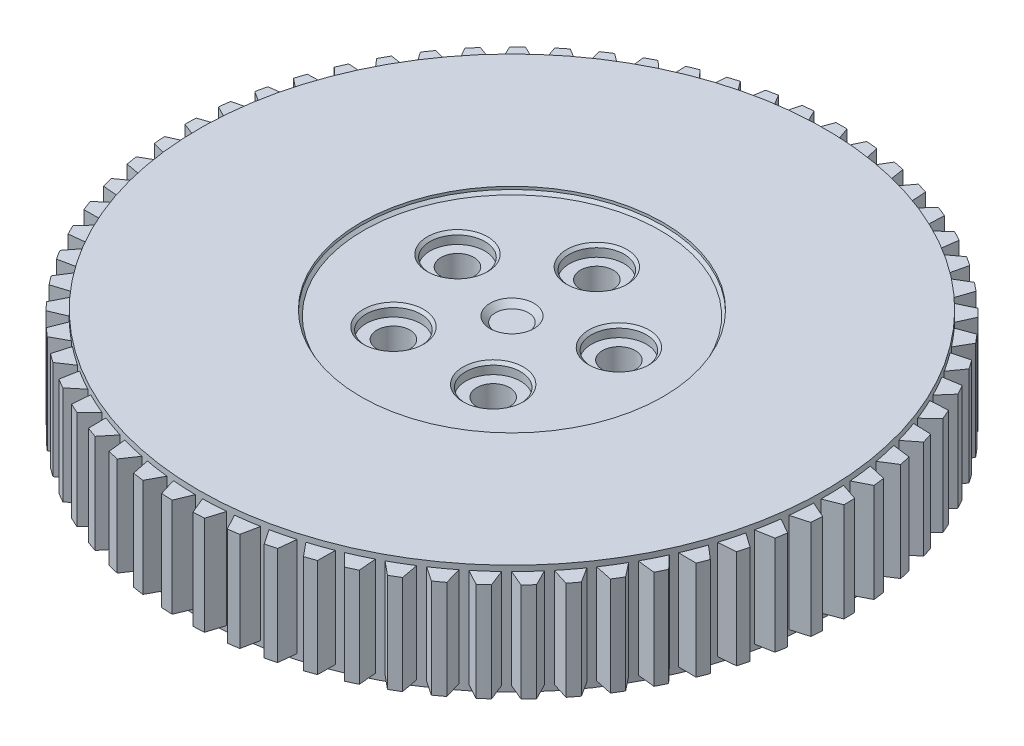
SolidWorks part; units mm, degrees
ref_plane "Front Plane" through (0, 0, 0) normal (0, 0, 1) x (1, 0, 0)
ref_plane "Top Plane" through (0, 0, 0) normal (0, 1, 0) x (1, 0, 0)
ref_plane "Right Plane" through (0, 0, 0) normal (1, 0, 0) x (0, 0, -1)
sketch "Sketch1" plane through (0, 0, 0) normal (0, 1, 0) x (1, 0, 0)
  circle A0 centre (0, 0) radius 114
  dimension "D1" = 228
extrude "Boss-Extrude1" add sketch "Sketch1" along normal blind 40
sketch "Sketch2" plane through (0, 40, 0) normal (0, 1, 0) x (1, 0, 0)
  line L1 (0, 30.9017) -> (-29.3893, 9.5492)
  line L2 (-29.3893, 9.5492) -> (-18.1636, -25)
  line L3 (-18.1636, -25) -> (18.1636, -25)
  line L4 (18.1636, -25) -> (29.3893, 9.5492)
  line L5 (29.3893, 9.5492) -> (0, 30.9017)
  circle A0 centre (0, 0) radius 25 construction
  circle A1 centre (0, 30.9017) radius 6
  circle A2 centre (-29.3893, 9.5492) radius 6
  circle A3 centre (-18.1636, -25) radius 6
  circle A4 centre (18.1636, -25) radius 6
  circle A5 centre (29.3893, 9.5492) radius 6
  dimension "D1" = 12
  dimension "D2" = 12
  dimension "D3" = 12
  dimension "D4" = 12
  dimension "D5" = 12
extrude "Cut-Extrude1" cut sketch "Sketch2" against normal blind 40 contours L1 A2 L2 | L2 A2 L1 | L1 A1 L5 | L5 A1 L1 | L5 A5 L4 | L4 A5 L5 | L3 A4 L4 | L4 A4 L3 | L2 A3 L3 | L3 A3 L2 region at (0, 40, -27.4681) region at (0, 40, -32.3732) region at (-26.1237, 40, -8.4881) region at (-30.7888, 40, -10.0039) region at (30.7888, 40, -10.0039) region at (26.1237, 40, -8.4881) region at (-16.1454, 40, 22.2222) region at (-19.0285, 40, 26.1905) region at (19.0285, 40, 26.1905) region at (16.1454, 40, 22.2222)
sketch "Sketch3" plane through (0, 0, 0) normal (0, -1, 0) x (1, 0, 0)
  circle A0 centre (0, 0) radius 45
  dimension "D1" = 90
extrude "Cut-Extrude2" cut sketch "Sketch3" against normal blind 15
sketch "Sketch4" plane through (0, 40, 0) normal (0, 1, 0) x (1, 0, 0)
  circle A5 centre (0, 30.9017) radius 10
  circle A6 centre (0, 30.9017) radius 10
  circle A8 centre (-29.3893, 9.5492) radius 10
  circle A9 centre (-29.3893, 9.5492) radius 10
  circle A11 centre (-18.1636, -25) radius 10
  circle A12 centre (-18.1636, -25) radius 10
  circle A14 centre (18.1636, -25) radius 10
  circle A15 centre (18.1636, -25) radius 10
  circle A17 centre (29.3893, 9.5492) radius 10
  circle A18 centre (29.3893, 9.5492) radius 10
  dimension "D1" = 4
  dimension "D2" = 4
  dimension "D3" = 4
  dimension "D4" = 4
  dimension "D5" = 4
extrude "Cut-Extrude3" cut sketch "Sketch4" against normal blind 6
chamfer "Chamfer1" distance 3 angle 45 5 edges at (-18.1636, 40, 35) (18.1636, 40, 35) (29.3893, 40, 0.4508) (-29.3893, 40, 0.4508) (0, 40, -20.9017)
sketch "Sketch5" plane through (0, 40, 0) normal (0, 1, 0) x (1, 0, 0)
  circle A0 centre (0, 0) radius 6
  dimension "D1" = 12
extrude "Cut-Extrude4" cut sketch "Sketch5" against normal blind 4
chamfer "Chamfer2" distance 4 angle 45 1 edges at (0, 40, 6)
sketch "Sketch8" plane through (0, 40, 0) normal (0, 1, 0) x (1, 0, 0)
  line L0 (0, 112) -> (0, 120)
  line L1 (-2, 120) -> (2, 120)
  line L2 (-2, 120) -> (-4.9516, 111.8905)
  line L3 (2, 120) -> (4.9516, 111.8905)
  line L4 (-4.9516, 111.8905) -> (4.9516, 111.8905)
  line L5 (5.8705, 111.846) -> (15.7275, 110.8902)
  line L6 (13.5723, 119.2468) -> (15.7275, 110.8902)
  line L7 (9.591, 119.6328) -> (13.5723, 119.2468)
  line L8 (9.591, 119.6328) -> (5.8705, 111.846)
  line L9 (16.6378, 110.7573) -> (26.3565, 108.8546)
  line L10 (25.0179, 117.3802) -> (26.3565, 108.8546)
  line L11 (21.0925, 118.1487) -> (25.0179, 117.3802)
  line L12 (21.0925, 118.1487) -> (16.6378, 110.7573)
  line L13 (27.2497, 108.6345) -> (36.7395, 105.8027)
  line L14 (36.23, 114.4176) -> (36.7395, 105.8027)
  line L15 (32.397, 115.5614) -> (36.23, 114.4176)
  line L16 (32.397, 115.5614) -> (27.2497, 108.6345)
  line L17 (37.6073, 105.4974) -> (46.7794, 101.7629)
  line L18 (47.1037, 110.3868) -> (46.7794, 101.7629)
  line L19 (43.399, 111.8951) -> (47.1037, 110.3868)
  line L20 (43.399, 111.8951) -> (37.6073, 105.4974)
  line L21 (47.6137, 101.3752) -> (56.3825, 96.773)
  line L22 (57.5377, 105.3253) -> (56.3825, 96.773)
  line L23 (53.9959, 107.1842) -> (57.5377, 105.3253)
  line L24 (53.9959, 107.1842) -> (47.6137, 101.3752)
  line L25 (57.1755, 96.3066) -> (65.4593, 90.8795)
  line L26 (67.4344, 99.2804) -> (65.4593, 90.8795)
  line L27 (64.0886, 101.4724) -> (67.4344, 99.2804)
  line L28 (64.0886, 101.4724) -> (57.1755, 96.3066)
  line L29 (66.2035, 90.3388) -> (73.9248, 84.1375)
  line L30 (76.7016, 92.3086) -> (73.9248, 84.1375)
  line L31 (73.5829, 94.8133) -> (76.7016, 92.3086)
  line L32 (73.5829, 94.8133) -> (66.2035, 90.3388)
  line L33 (74.6134, 83.5275) -> (81.7002, 76.61)
  line L34 (85.2526, 84.4749) -> (81.7002, 76.61)
  line L35 (82.3902, 87.2689) -> (85.2526, 84.4749)
  line L36 (82.3902, 87.2689) -> (74.6134, 83.5275)
  line L37 (82.3266, 75.9363) -> (88.7127, 68.3671)
  line L38 (93.0076, 75.8524) -> (88.7127, 68.3671)
  line L39 (90.4282, 78.9097) -> (93.0076, 75.8524)
  line L40 (90.4282, 78.9097) -> (82.3266, 75.9363)
  line L41 (89.2712, 67.6361) -> (94.8969, 59.4859)
  line L42 (99.8942, 66.5218) -> (94.8969, 59.4859)
  line L43 (97.6219, 69.8137) -> (99.8942, 66.5218)
  line L44 (97.6219, 69.8137) -> (89.2712, 67.6361)
  line L45 (95.3823, 58.7045) -> (100.1951, 50.0494)
  line L46 (105.8481, 56.5701) -> (100.1951, 50.0494)
  line L47 (103.9042, 60.0659) -> (105.8481, 56.5701)
  line L48 (103.9042, 60.0659) -> (95.3823, 58.7045)
  line L49 (100.6028, 49.2247) -> (104.5578, 40.1455)
  line L50 (110.8138, 46.0902) -> (104.5578, 40.1455)
  line L51 (109.2163, 49.7573) -> (110.8138, 46.0902)
  line L52 (109.2163, 49.7573) -> (100.6028, 49.2247)
  line L53 (104.884, 39.2853) -> (107.9443, 29.8668)
  line L54 (114.7448, 35.1799) -> (107.9443, 29.8668)
  line L55 (113.5087, 38.9842) -> (114.7448, 35.1799)
  line L56 (113.5087, 38.9842) -> (104.884, 39.2853)
  line L57 (108.186, 28.9792) -> (110.323, 19.3092)
  line L58 (117.6045, 23.9412) -> (110.323, 19.3092)
  line L59 (116.7414, 27.847) -> (117.6045, 23.9412)
  line L60 (116.7414, 27.847) -> (108.186, 28.9792)
  line L61 (110.4778, 18.4024) -> (111.6715, 8.5714)
  line L62 (119.3661, 12.479) -> (111.6715, 8.5714)
  line L63 (118.884, 16.4498) -> (119.3661, 12.479)
  line L64 (118.884, 16.4498) -> (110.4778, 18.4024)
  line L65 (111.7382, 7.6539) -> (111.9775, -2.2465)
  line L66 (120.0133, 0.9002) -> (111.9775, -2.2465)
  line L67 (119.9166, 4.8991) -> (120.0133, 0.9002)
  line L68 (119.9166, 4.8991) -> (111.7382, 7.6539)
  line L69 (111.9552, -3.1662) -> (111.2379, -13.0434)
  line L70 (119.5399, -10.6869) -> (111.2379, -13.0434)
  line L71 (119.8296, -6.6974) -> (119.5399, -10.6869)
  line L72 (119.8296, -6.6974) -> (111.9552, -3.1662)
  line L73 (111.127, -13.9566) -> (109.4597, -23.7185)
  line L74 (117.9504, -22.1743) -> (109.4597, -23.7185)
  line L75 (118.6238, -18.2314) -> (117.9504, -22.1743)
  line L76 (118.6238, -18.2314) -> (111.127, -13.9566)
  line L77 (109.2612, -24.6168) -> (106.6596, -34.1722)
  line L78 (115.2597, -33.4546) -> (106.6596, -34.1722)
  line L79 (116.3105, -29.5951) -> (115.2597, -33.4546)
  line L80 (116.3105, -29.5951) -> (109.2612, -24.6168)
  line L81 (106.3753, -35.0471) -> (102.8636, -44.3068)
  line L82 (111.4927, -44.4226) -> (102.8636, -44.3068)
  line L83 (112.9112, -40.6826) -> (111.4927, -44.4226)
  line L84 (112.9112, -40.6826) -> (106.3753, -35.0471)
  line L85 (102.4962, -45.1502) -> (98.1071, -54.0277)
  line L86 (106.6848, -54.9758) -> (98.1071, -54.0277)
  line L87 (108.4576, -51.3901) -> (106.6848, -54.9758)
  line L88 (108.4576, -51.3901) -> (102.4962, -45.1502)
  line L89 (97.6601, -54.8317) -> (92.4347, -63.2442)
  line L90 (100.8809, -65.0158) -> (92.4347, -63.2442)
  line L91 (102.9914, -61.6179) -> (100.8809, -65.0158)
  line L92 (102.9914, -61.6179) -> (97.6601, -54.8317)
  line L93 (91.9121, -64.0013) -> (85.8992, -71.8702)
  line L94 (94.135, -74.4487) -> (85.8992, -71.8702)
  line L95 (96.5636, -71.2703) -> (94.135, -74.4487)
  line L96 (96.5636, -71.2703) -> (91.9121, -64.0013)
  line L97 (85.306, -72.5733) -> (78.5618, -79.8251)
  line L98 (86.5102, -83.1864) -> (78.5618, -79.8251)
  line L99 (89.2343, -80.2574) -> (86.5102, -83.1864)
  line L100 (89.2343, -80.2574) -> (85.306, -72.5733)
  line L101 (77.9035, -80.4677) -> (70.4908, -87.0348)
  line L102 (78.0777, -91.1475) -> (70.4908, -87.0348)
  line L103 (81.0717, -88.495) -> (78.0777, -91.1475)
  line L104 (81.0717, -88.495) -> (77.9035, -80.4677)
  line L105 (69.7735, -87.6108) -> (61.7616, -93.4318)
  line L106 (68.9162, -98.2576) -> (61.7616, -93.4318)
  line L107 (72.1523, -95.9065) -> (68.9162, -98.2576)
  line L108 (72.1523, -95.9065) -> (69.7735, -87.6108)
  line L109 (60.9921, -93.9359) -> (52.4558, -98.9565)
  line L110 (59.1112, -104.4503) -> (52.4558, -98.9565)
  line L111 (62.5591, -102.4224) -> (59.1112, -104.4503)
  line L112 (62.5591, -102.4224) -> (60.9921, -93.9359)
  line L113 (51.6413, -99.384) -> (42.6603, -103.5572)
  line L114 (48.7544, -109.6677) -> (42.6603, -103.5572)
  line L115 (52.3819, -107.9821) -> (48.7544, -109.6677)
  line L116 (52.3819, -107.9821) -> (51.6413, -99.384)
  line L117 (41.8083, -103.9041) -> (32.4664, -107.1911)
  line L118 (37.9423, -113.8612) -> (32.4664, -107.1911)
  line L119 (41.7156, -112.5336) -> (37.9423, -113.8612)
  line L120 (41.7156, -112.5336) -> (41.8083, -103.9041)
  line L121 (31.5849, -107.4542) -> (21.9694, -109.8242)
  line L122 (26.776, -116.9916) -> (21.9694, -109.8242)
  line L123 (30.6598, -116.0344) -> (26.776, -116.9916)
  line L124 (30.6598, -116.0344) -> (31.5849, -107.4542)
  line L125 (21.0666, -110.0009) -> (11.2673, -111.4318)
  line L126 (15.3597, -119.0297) -> (11.2673, -111.4318)
  line L127 (19.3177, -118.4518) -> (15.3597, -119.0297)
  line L128 (19.3177, -118.4518) -> (21.0666, -110.0009)
  line L129 (10.3516, -111.5206) -> (0.46, -111.9991)
  line L130 (3.7999, -119.9565) -> (0.46, -111.9991)
  line L131 (7.7953, -119.7632) -> (3.7999, -119.9565)
  line L132 (7.7953, -119.7632) -> (10.3516, -111.5206)
  line L133 (-0.46, -111.9991) -> (-10.3516, -111.5206)
  line L134 (-7.7953, -119.7632) -> (-10.3516, -111.5206)
  line L135 (-3.7999, -119.9565) -> (-7.7953, -119.7632)
  line L136 (-3.7999, -119.9565) -> (-0.46, -111.9991)
  line L137 (-11.2673, -111.4318) -> (-21.0666, -110.0009)
  line L138 (-19.3177, -118.4518) -> (-21.0666, -110.0009)
  line L139 (-15.3597, -119.0297) -> (-19.3177, -118.4518)
  line L140 (-15.3597, -119.0297) -> (-11.2673, -111.4318)
  line L141 (-21.9694, -109.8242) -> (-31.5849, -107.4542)
  line L142 (-30.6598, -116.0344) -> (-31.5849, -107.4542)
  line L143 (-26.776, -116.9916) -> (-30.6598, -116.0344)
  line L144 (-26.776, -116.9916) -> (-21.9694, -109.8242)
  line L145 (-32.4664, -107.1911) -> (-41.8083, -103.9041)
  line L146 (-41.7156, -112.5336) -> (-41.8083, -103.9041)
  line L147 (-37.9423, -113.8612) -> (-41.7156, -112.5336)
  line L148 (-37.9423, -113.8612) -> (-32.4664, -107.1911)
  line L149 (-42.6603, -103.5572) -> (-51.6413, -99.384)
  line L150 (-52.3819, -107.9821) -> (-51.6413, -99.384)
  line L151 (-48.7544, -109.6677) -> (-52.3819, -107.9821)
  line L152 (-48.7544, -109.6677) -> (-42.6603, -103.5572)
  line L153 (-52.4558, -98.9565) -> (-60.9921, -93.9359)
  line L154 (-62.5591, -102.4224) -> (-60.9921, -93.9359)
  line L155 (-59.1112, -104.4503) -> (-62.5591, -102.4224)
  line L156 (-59.1112, -104.4503) -> (-52.4558, -98.9565)
  line L157 (-61.7616, -93.4318) -> (-69.7735, -87.6108)
  line L158 (-72.1523, -95.9065) -> (-69.7735, -87.6108)
  line L159 (-68.9162, -98.2576) -> (-72.1523, -95.9065)
  line L160 (-68.9162, -98.2576) -> (-61.7616, -93.4318)
  line L161 (-70.4908, -87.0348) -> (-77.9035, -80.4677)
  line L162 (-81.0717, -88.495) -> (-77.9035, -80.4677)
  line L163 (-78.0777, -91.1475) -> (-81.0717, -88.495)
  line L164 (-78.0777, -91.1475) -> (-70.4908, -87.0348)
  line L165 (-78.5618, -79.8251) -> (-85.306, -72.5733)
  line L166 (-89.2343, -80.2574) -> (-85.306, -72.5733)
  line L167 (-86.5102, -83.1864) -> (-89.2343, -80.2574)
  line L168 (-86.5102, -83.1864) -> (-78.5618, -79.8251)
  line L169 (-85.8992, -71.8702) -> (-91.9121, -64.0013)
  line L170 (-96.5636, -71.2703) -> (-91.9121, -64.0013)
  line L171 (-94.135, -74.4487) -> (-96.5636, -71.2703)
  line L172 (-94.135, -74.4487) -> (-85.8992, -71.8702)
  line L173 (-92.4347, -63.2442) -> (-97.6601, -54.8317)
  line L174 (-102.9914, -61.6179) -> (-97.6601, -54.8317)
  line L175 (-100.8809, -65.0158) -> (-102.9914, -61.6179)
  line L176 (-100.8809, -65.0158) -> (-92.4347, -63.2442)
  line L177 (-98.1071, -54.0277) -> (-102.4962, -45.1502)
  line L178 (-108.4576, -51.3901) -> (-102.4962, -45.1502)
  line L179 (-106.6848, -54.9758) -> (-108.4576, -51.3901)
  line L180 (-106.6848, -54.9758) -> (-98.1071, -54.0277)
  line L181 (-102.8636, -44.3068) -> (-106.3753, -35.0471)
  line L182 (-112.9112, -40.6826) -> (-106.3753, -35.0471)
  line L183 (-111.4927, -44.4226) -> (-112.9112, -40.6826)
  line L184 (-111.4927, -44.4226) -> (-102.8636, -44.3068)
  line L185 (-106.6596, -34.1722) -> (-109.2612, -24.6168)
  line L186 (-116.3105, -29.5951) -> (-109.2612, -24.6168)
  line L187 (-115.2597, -33.4546) -> (-116.3105, -29.5951)
  line L188 (-115.2597, -33.4546) -> (-106.6596, -34.1722)
  line L189 (-109.4597, -23.7185) -> (-111.127, -13.9566)
  line L190 (-118.6238, -18.2314) -> (-111.127, -13.9566)
  line L191 (-117.9504, -22.1743) -> (-118.6238, -18.2314)
  line L192 (-117.9504, -22.1743) -> (-109.4597, -23.7185)
  line L193 (-111.2379, -13.0434) -> (-111.9552, -3.1662)
  line L194 (-119.8296, -6.6974) -> (-111.9552, -3.1662)
  line L195 (-119.5399, -10.6869) -> (-119.8296, -6.6974)
  line L196 (-119.5399, -10.6869) -> (-111.2379, -13.0434)
  line L197 (-111.9775, -2.2465) -> (-111.7382, 7.6539)
  line L198 (-119.9166, 4.8991) -> (-111.7382, 7.6539)
  line L199 (-120.0133, 0.9002) -> (-119.9166, 4.8991)
  line L200 (-120.0133, 0.9002) -> (-111.9775, -2.2465)
  line L201 (-111.6715, 8.5714) -> (-110.4778, 18.4024)
  line L202 (-118.884, 16.4498) -> (-110.4778, 18.4024)
  line L203 (-119.3661, 12.479) -> (-118.884, 16.4498)
  line L204 (-119.3661, 12.479) -> (-111.6715, 8.5714)
  line L205 (-110.323, 19.3092) -> (-108.186, 28.9792)
  line L206 (-116.7414, 27.847) -> (-108.186, 28.9792)
  line L207 (-117.6045, 23.9412) -> (-116.7414, 27.847)
  line L208 (-117.6045, 23.9412) -> (-110.323, 19.3092)
  line L209 (-107.9443, 29.8668) -> (-104.884, 39.2853)
  line L210 (-113.5087, 38.9842) -> (-104.884, 39.2853)
  line L211 (-114.7448, 35.1799) -> (-113.5087, 38.9842)
  line L212 (-114.7448, 35.1799) -> (-107.9443, 29.8668)
  line L213 (-104.5578, 40.1455) -> (-100.6028, 49.2247)
  line L214 (-109.2163, 49.7573) -> (-100.6028, 49.2247)
  line L215 (-110.8138, 46.0902) -> (-109.2163, 49.7573)
  line L216 (-110.8138, 46.0902) -> (-104.5578, 40.1455)
  line L217 (-100.1951, 50.0494) -> (-95.3823, 58.7045)
  line L218 (-103.9042, 60.0659) -> (-95.3823, 58.7045)
  line L219 (-105.8481, 56.5701) -> (-103.9042, 60.0659)
  line L220 (-105.8481, 56.5701) -> (-100.1951, 50.0494)
  line L221 (-94.8969, 59.4859) -> (-89.2712, 67.6361)
  line L222 (-97.6219, 69.8137) -> (-89.2712, 67.6361)
  line L223 (-99.8942, 66.5218) -> (-97.6219, 69.8137)
  line L224 (-99.8942, 66.5218) -> (-94.8969, 59.4859)
  line L225 (-88.7127, 68.3671) -> (-82.3266, 75.9363)
  line L226 (-90.4282, 78.9097) -> (-82.3266, 75.9363)
  line L227 (-93.0076, 75.8524) -> (-90.4282, 78.9097)
  line L228 (-93.0076, 75.8524) -> (-88.7127, 68.3671)
  line L229 (-81.7002, 76.61) -> (-74.6134, 83.5275)
  line L230 (-82.3902, 87.2689) -> (-74.6134, 83.5275)
  line L231 (-85.2526, 84.4749) -> (-82.3902, 87.2689)
  line L232 (-85.2526, 84.4749) -> (-81.7002, 76.61)
  line L233 (-73.9248, 84.1375) -> (-66.2035, 90.3388)
  line L234 (-73.5829, 94.8133) -> (-66.2035, 90.3388)
  line L235 (-76.7016, 92.3086) -> (-73.5829, 94.8133)
  line L236 (-76.7016, 92.3086) -> (-73.9248, 84.1375)
  line L237 (-65.4593, 90.8795) -> (-57.1755, 96.3066)
  line L238 (-64.0886, 101.4724) -> (-57.1755, 96.3066)
  line L239 (-67.4344, 99.2804) -> (-64.0886, 101.4724)
  line L240 (-67.4344, 99.2804) -> (-65.4593, 90.8795)
  line L241 (-56.3825, 96.773) -> (-47.6137, 101.3752)
  line L242 (-53.9959, 107.1842) -> (-47.6137, 101.3752)
  line L243 (-57.5377, 105.3253) -> (-53.9959, 107.1842)
  line L244 (-57.5377, 105.3253) -> (-56.3825, 96.773)
  line L245 (-46.7794, 101.7629) -> (-37.6073, 105.4974)
  line L246 (-43.399, 111.8951) -> (-37.6073, 105.4974)
  line L247 (-47.1037, 110.3868) -> (-43.399, 111.8951)
  line L248 (-47.1037, 110.3868) -> (-46.7794, 101.7629)
  line L249 (-36.7395, 105.8027) -> (-27.2497, 108.6345)
  line L250 (-32.397, 115.5614) -> (-27.2497, 108.6345)
  line L251 (-36.23, 114.4176) -> (-32.397, 115.5614)
  line L252 (-36.23, 114.4176) -> (-36.7395, 105.8027)
  line L253 (-26.3565, 108.8546) -> (-16.6378, 110.7573)
  line L254 (-21.0925, 118.1487) -> (-16.6378, 110.7573)
  line L255 (-25.0179, 117.3802) -> (-21.0925, 118.1487)
  line L256 (-25.0179, 117.3802) -> (-26.3565, 108.8546)
  line L257 (-15.7275, 110.8902) -> (-5.8705, 111.846)
  line L258 (-9.591, 119.6328) -> (-5.8705, 111.846)
  line L259 (-13.5723, 119.2468) -> (-9.591, 119.6328)
  line L260 (-13.5723, 119.2468) -> (-15.7275, 110.8902)
  circle A0 centre (0, 0) radius 112
  circle A1 centre (0, 0) radius 120
  point P9 (0, 120)
  point P270 (0, 0)
  circle M12 centre (0, 0) radius 114
  dimension "D1" = 240
  dimension "D2" = 224
  dimension "D3" = 4
  dimension "D4" = 110
  dimension "D5" = 110
  dimension "D6" = 65
extrude "Boss-Extrude2" add sketch "Sketch8" against normal blind 38 contours L238 A1 L240 M12 | L242 A1 L244 M12 | L246 A1 L248 M12 | L250 A1 L252 M12 | A0 L246 L248 M12 | A0 L242 L244 M12 | A0 L250 L252 M12 | A0 L254 L256 M12 | L254 A1 L256 M12 | A0 L258 L260 M12 | L258 A1 L260 M12 | A0 L0 L2 M12 | L0 A1 L2 M12 | L3 A1 L0 M12 | A0 L3 L0 M12 | A0 L6 L8 M12 | L6 A1 L8 M12 | A0 L10 L12 M12 | L10 A1 L12 M12 | A0 L14 L16 M12 | L14 A1 L16 M12 | A0 L18 L20 M12 | L18 A1 L20 M12 | A0 L22 L24 M12 | L22 A1 L24 M12 | A0 L26 L28 M12 | L26 A1 L28 M12 | A0 L30 L32 M12 | L30 A1 L32 M12 | A0 L34 L36 M12 | L34 A1 L36 M12 | A0 L38 L40 M12 | L38 A1 L40 M12 | A0 L42 L44 M12 | L42 A1 L44 M12 | A0 L46 L48 M12 | L46 A1 L48 M12 | A0 L50 L52 M12 | L50 A1 L52 M12 | A0 L54 L56 M12 | L54 A1 L56 M12 | A0 L58 L60 M12 | L58 A1 L60 M12 | A0 L62 L64 M12 | L62 A1 L64 M12 | A0 L66 L68 M12 | L66 A1 L68 M12 | A0 L70 L72 M12 | L70 A1 L72 M12 | A0 L74 L76 M12 | L74 A1 L76 M12 | A0 L78 L80 M12 | L78 A1 L80 M12 | A0 L82 L84 M12 | L82 A1 L84 M12 | L94 A1 L96 M12 | A0 L94 L96 M12 | A0 L90 L92 M12 | L90 A1 L92 M12 | L86 A1 L88 M12 | A0 L86 L88 M12 | A0 L102 L104 M12 | L102 A1 L104 M12 | L98 A1 L100 M12 | A0 L98 L100 M12 | L106 A1 L108 M12 | A0 L106 L108 M12 | A0 L114 L116 M12 | L114 A1 L116 M12 | L118 A1 L120 M12 | A0 L118 L120 M12 | L122 A1 L124 M12 | A0 L122 L124 M12 | L110 A1 L112 M12 | A0 L110 L112 M12 | L126 A1 L128 M12 | A0 L126 L128 M12 | A0 L130 L132 M12 | L130 A1 L132 M12 | L134 A1 L136 M12 | A0 L134 L136 M12 | A0 L138 L140 M12 | L138 A1 L140 M12 | L142 A1 L144 M12 | A0 L142 L144 M12 | A0 L146 L148 M12 | L146 A1 L148 M12 | L150 A1 L152 M12 | A0 L150 L152 M12 | L154 A1 L156 M12 | A0 L154 L156 M12 | L158 A1 L160 M12 | A0 L158 L160 M12 | L162 A1 L164 M12 | A0 L162 L164 M12 | L166 A1 L168 M12 | A0 L166 L168 M12 | L170 A1 L172 M12 | A0 L170 L172 M12 | L174 A1 L176 M12 | A0 L174 L176 M12 | L178 A1 L180 M12 | A0 L178 L180 M12 | L182 A1 L184 M12 | A0 L182 L184 M12 | L186 A1 L188 M12 | A0 L186 L188 M12 | L190 A1 L192 M12 | A0 L190 L192 M12 | L194 A1 L196 M12 | A0 L194 L196 M12 | L198 A1 L200 M12 | A0 L198 L200 M12 | L202 A1 L204 M12 | A0 L202 L204 M12 | L206 A1 L208 M12 | A0 L206 L208 M12 | A0 L210 L212 M12 | L210 A1 L212 M12 | L214 A1 L216 M12 | A0 L214 L216 M12 | A0 L218 L220 M12 | L218 A1 L220 M12 | A0 L222 L224 M12 | L222 A1 L224 M12 | A0 L226 L228 M12 | L226 A1 L228 M12 | A0 L230 L232 M12 | L230 A1 L232 M12 | A0 L234 L236 M12 | L234 A1 L236 M12 region at (-2.2961, 40, -112.9419) region at (2.2961, 40, -112.9419) region at (-1.6192, 40, -116.6294) region at (1.6192, 40, -116.6294) region at (10.9005, 40, -112.4146) region at (-10.9005, 40, -112.4146) region at (11.2564, 40, -116.0849) region at (-11.2564, 40, -116.0849) region at (21.6992, 40, -110.8378) region at (-21.6992, 40, -110.8378) region at (22.4076, 40, -114.4566) region at (-22.4076, 40, -114.4566) region at (32.2952, 40, -108.2261) region at (-32.2952, 40, -108.2261) region at (33.3497, 40, -111.7596) region at (-33.3497, 40, -111.7596) region at (42.5898, 40, -104.6039) region at (-42.5898, 40, -104.6039) region at (43.9803, 40, -108.0192) region at (-43.9803, 40, -108.0192) region at (52.4867, 40, -100.0051) region at (-52.4867, 40, -100.0051) region at (54.2004, 40, -103.2702) region at (-54.2004, 40, -103.2702) region at (61.8936, 40, -94.4725) region at (63.9143, 40, -97.557) region at (-63.9143, 40, -97.557) region at (70.7225, 40, -88.0579) region at (-70.7225, 40, -88.0579) region at (73.0316, 40, -90.9329) region at (-73.0316, 40, -90.9329) region at (78.8912, 40, -80.8211) region at (-78.8912, 40, -80.8211) region at (81.4669, 40, -83.4598) region at (-81.4669, 40, -83.4598) region at (86.3233, 40, -72.8297) region at (-86.3233, 40, -72.8297) region at (89.1416, 40, -75.2075) region at (-89.1416, 40, -75.2075) region at (92.9493, 40, -64.1583) region at (-92.9493, 40, -64.1583) region at (95.9841, 40, -66.253) region at (-95.9841, 40, -66.253) region at (98.7076, 40, -54.8879) region at (-98.7076, 40, -54.8879) region at (101.9303, 40, -56.6799) region at (-101.9303, 40, -56.6799) region at (103.5442, 40, -45.105) region at (-103.5442, 40, -45.105) region at (106.9249, 40, -46.5776) region at (-106.9249, 40, -46.5776) region at (107.4141, 40, -34.901) region at (-107.4141, 40, -34.901) region at (110.9211, 40, -36.0405) region at (-110.9211, 40, -36.0405) region at (110.2811, 40, -24.3711) region at (-110.2811, 40, -24.3711) region at (113.8817, 40, -25.1668) region at (-113.8817, 40, -25.1668) region at (112.1184, 40, -13.6136)
sketch "Sketch9" plane through (0, 40, 0) normal (0, 1, 0) x (1, 0, 0)
  circle A0 centre (0, 0) radius 114
  circle A1 centre (0, 0) radius 120
extrude "Cut-Extrude5" cut sketch "Sketch9" against normal blind 2
sketch "Sketch10" plane through (0, 40, 0) normal (0, 1, 0) x (1, 0, 0)
  circle A0 centre (0, 0) radius 55
  dimension "D1" = 110
extrude "Cut-Extrude6" cut sketch "Sketch10" against normal blind 2
chamfer "Chamfer3" distance 1 angle 45 1 edges at (0, 38, 55)
